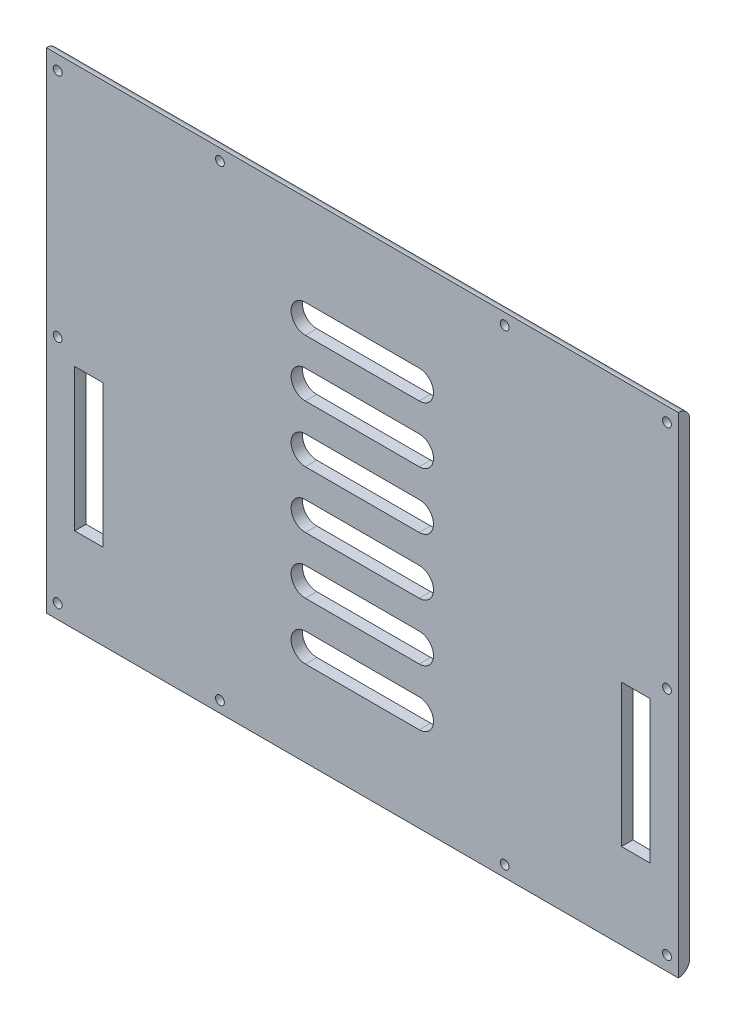
SolidWorks part; units mm, degrees
ref_plane "Front Plane" through (0, 0, 0) normal (1, 0, 0) x (0, 1, 0)
ref_plane "Top Plane" through (0, 0, 0) normal (0, 0, 1) x (0, 1, 0)
ref_plane "Right Plane" through (0, 0, 0) normal (0, 1, 0) x (-1, 0, 0)
sketch "Sketch1" plane through (0, 0, 0) normal (0, 0, 1) x (0, 1, 0)
  line L0 (86, 222) -> (86, 0) construction
  line L1 (0, 0) -> (172, 0)
  line L2 (0, 0) -> (0, 222)
  line L3 (0, 222) -> (172, 222)
  line L4 (172, 0) -> (172, 222)
  line L5 (35, 131) -> (35, 91) construction
  line L6 (30, 212) -> (80, 212)
  line L7 (30, 212) -> (30, 202)
  line L8 (30, 202) -> (80, 202)
  line L9 (80, 212) -> (80, 202)
  line L10 (30, 20) -> (80, 20)
  line L11 (30, 20) -> (30, 10)
  line L12 (30, 10) -> (80, 10)
  line L13 (80, 20) -> (80, 10)
  line L14 (40, 131) -> (40, 91)
  line L15 (30, 131) -> (30, 91)
  line L16 (0, 111) -> (191, 111) construction
  line L17 (55, 131) -> (55, 91) construction
  line L18 (60, 131) -> (60, 91)
  line L19 (50, 131) -> (50, 91)
  line L20 (75, 131) -> (75, 91) construction
  line L21 (80, 131) -> (80, 91)
  line L22 (70, 131) -> (70, 91)
  line L23 (95, 131) -> (95, 91) construction
  line L24 (100, 131) -> (100, 91)
  line L25 (90, 131) -> (90, 91)
  line L26 (115, 131) -> (115, 91) construction
  line L27 (120, 131) -> (120, 91)
  line L28 (110, 131) -> (110, 91)
  line L29 (135, 131) -> (135, 91) construction
  line L30 (140, 131) -> (140, 91)
  line L31 (130, 131) -> (130, 91)
  line L98 (155, 121) -> (155, 81) construction
  line L99 (160, 121) -> (160, 81)
  line L100 (150, 121) -> (150, 81)
  line L101 (155, 131) -> (155, 91) construction
  line L102 (160, 131) -> (160, 91)
  line L103 (150, 131) -> (150, 91)
  circle A0 centre (5, 4) radius 1.55
  circle A1 centre (5, 218) radius 1.55
  circle A2 centre (167, 218) radius 1.55
  circle A3 centre (167, 4) radius 1.55
  circle A4 centre (86, 218) radius 1.55
  circle A5 centre (86, 4) radius 1.55
  arc A6 (40, 131) -> (30, 131) centre (35, 131) ccw
  arc A7 (30, 91) -> (40, 91) centre (35, 91) ccw
  arc A8 (60, 131) -> (50, 131) centre (55, 131) ccw
  arc A9 (50, 91) -> (60, 91) centre (55, 91) ccw
  arc A10 (80, 131) -> (70, 131) centre (75, 131) ccw
  arc A11 (70, 91) -> (80, 91) centre (75, 91) ccw
  arc A12 (100, 131) -> (90, 131) centre (95, 131) ccw
  arc A13 (90, 91) -> (100, 91) centre (95, 91) ccw
  arc A14 (120, 131) -> (110, 131) centre (115, 131) ccw
  arc A15 (110, 91) -> (120, 91) centre (115, 91) ccw
  arc A16 (140, 131) -> (130, 131) centre (135, 131) ccw
  arc A17 (130, 91) -> (140, 91) centre (135, 91) ccw
  circle A20 centre (4, 61) radius 1.55
  circle A21 centre (168, 61) radius 1.55
  circle A22 centre (168, 161) radius 1.55
  circle A23 centre (4, 161) radius 1.55
  arc A68 (160, 131) -> (150, 131) centre (155, 131) ccw
  arc A69 (150, 91) -> (160, 91) centre (155, 91) ccw
  point P29 (35, 111)
  point P37 (0, 111)
  point P41 (55, 111)
  point P48 (75, 111)
  point P55 (95, 111)
  point P62 (115, 111)
  point P69 (135, 111)
  point P74 (0, 0)
  point P75 (5, 128)
  point P76 (0, 0)
  point P77 (5, 28)
  point P78 (0, 0)
  point P89 (155, 73)
  point P96 (155, 73)
  point P103 (155, 76)
  point P110 (155, 76)
  point P117 (155, 76)
  point P124 (155, 76)
  point P131 (155, 76)
  point P138 (155, 76)
  point P145 (155, 78)
  point P152 (155, 78)
  point P159 (155, 78)
  point P166 (155, 78)
  point P173 (155, 78)
  point P180 (155, 78)
  point P187 (155, 78)
  point P194 (155, 78)
  point P201 (155, 78)
  point P208 (155, 78)
  point P215 (155, 90.5)
  point P222 (155, 90.5)
  point P229 (155, 101)
  point P236 (155, 101)
  point P243 (155, 111)
  dimension "D7" = 3.1
  dimension "D1" = 172
  dimension "D2" = 222
  dimension "D3" = 4
  dimension "D4" = 5
  dimension "D5" = 4
  dimension "D6" = 5
  dimension "D8" = 30
  dimension "D9" = 10
  dimension "D10" = 10
  dimension "D11" = 10
  dimension "D12" = 50
  dimension "D13" = 10
  dimension "D14" = 40
  dimension "D16" = 10
  dimension "D17" = 50
  dimension "D18" = 4
  dimension "D19" = 4
  dimension "D15" = 7
extrude "Boss-Extrude2" add sketch "Sketch1" along normal blind 4
fillet "Fillet1" radius 4 2 edges at (-111, 172, 0) (-111, 0, 0)
equation "\"MotorDriverLength\"= 60mm"
equation "\"MotorLength\"= 60"
equation "\"MotorDriverWidth\"=44"
equation "\"MotorWidth\"= 37"
equation "\"InnerWallThickness\"=3"
equation "\"BatteryWidth\"= 60"
equation "\"OuterWallThickness\" = 8"
equation "\"CompartmentHeight\"=37"
equation "\"CompartmentWidth\"= \"MotorDriverLength\""
equation "\"MotorDiameter\"=37"
equation "\"BatteryHeight\"=24.2019"
equation "\"MotorDriverHeight\"=28"
equation "\"CircuitHeight\"=30"
equation "\"FanThickness\"= 10"
equation "\"FanHeight\"=50"
equation "\"MotorShaftHole\"=12"
equation "\"BearingBore\"=4"
equation "\"MinShinWidth\"= 20"
equation "\"ShinThickness\"=10"
equation "\"PivotDistance\"=30"
equation "\"ThighLength\"= 200"
equation "\"KneeLength\" =20"
equation "\"HipBore\"=27"
equation "\"ThighThickness\"=20"
equation "\"MaxBending\"=135"
equation "\"MaxStretchingAngle\"= 140"
equation "\"ThighJointDistance\"=157.485"
equation "\"ShinLength\"=120"
equation "\"BearingDiameter\"= 10"
equation "\"CircuitLength\"=50"
equation "\"ChessisInnerWidth\"= \"OuterWallThickness\" * 2 + \"MotorDriverLength\" + \"MotorDiameter\" + \"InnerWallThickness\" * 3 + \"CircuitLength\""
equation "\"D1@Sketch1\"=\"ChessisInnerWidth\""
equation "\"D2@Sketch1\"= \"ChassisWidth\" + \"OuterWallThickness\" * 2"
equation "\"ChassisWidth\"= \"MotorDriverWidth\"*4+30"
equation "\"D3@Sketch1\"=\"OuterWallThickness\"/2"
equation "\"D18@Sketch1\"=\"OuterWallThickness\"/2"
equation "\"D19@Sketch1\"=\"OuterWallThickness\"/2"
equation "\"D5@Sketch1\"=\"OuterWallThickness\"/2"
